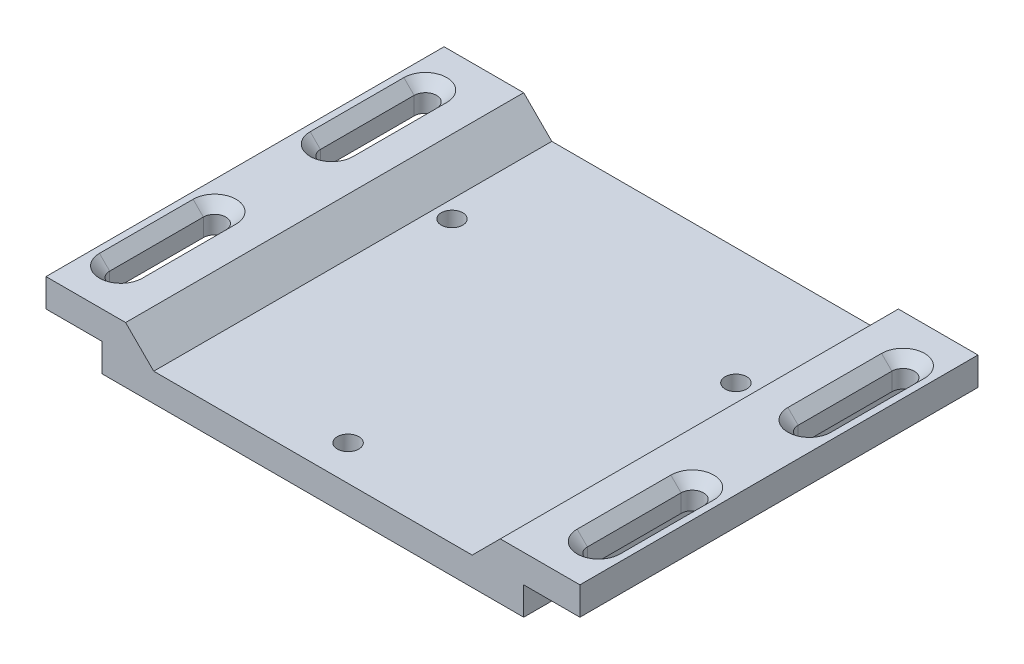
SolidWorks part; units mm, degrees
note: '?' marks a value the reader was unsure of. The reader was unsure of these and kept them because the rebuilt part matched: shared geometry of "Sketch16<4>".
ref_plane "Płaszczyzna przednia" through (0, 0, 0) normal (0, 0, 1) x (1, 0, 0)
ref_plane "Płaszczyzna górna" through (0, 0, 0) normal (0, 1, 0) x (1, 0, 0)
ref_plane "Płaszczyzna prawa" through (0, 0, 0) normal (1, 0, 0) x (0, 0, -1)
sketch "Sketch1" plane through (0, 0, 0) normal (0, 1, 0) x (1, 0, 0)
  line L1 (0, 0) -> (90, 0)
  line L2 (0, 0) -> (0, 85)
  line L3 (0, 85) -> (90, 85)
  line L4 (90, 0) -> (90, 85)
  dimension "D1" = 90
  dimension "D2" = 85
extrude "Boss-Extrude1" add sketch "Sketch1" along normal blind 6
fillet "Fillet1" [suppressed] radius 5
hole_wizard "Ø4.6 (4.6) Diameter Hole1" positions "Sketch4" profile "Sketch5" hole size "Ø4.6" standard "DIN" end condition through all
sketch "Sketch4" plane through (0, 6, 0) normal (0, 1, 0) x (1, 0, 0)
  line L1 (0, 85) -> (90, 85) construction
  line L2 (0, 85) -> (0, 0) construction
  line L3 (0, 0) -> (90, 0) construction
  line L4 (90, 85) -> (90, 0) construction
  line L5 (90, 85) -> (0, 85) construction
  line L6 (0, 85) -> (0, 0) construction
  line L7 (0, 0) -> (90, 85) construction
  line L9 (90, 0) -> (0, 85) construction
  line L10 (45, 40) -> (45, 5) construction
  line L11 (75.3109, 60) -> (14.6891, 60) construction
  circle A0 centre (45, 42.5) radius 35 construction
  point P81 (45, 7.5)
  point P88 (14.6891, 60)
  point P89 (75.3109, 60)
  dimension "D1" = 70
  dimension "D2" = 3
sketch "Sketch5" plane through (75.3109, 6, -60) normal (1, 0, 0) x (0, 0, 1)
  line L0 (0, 0) -> (0, 6)
  line L1 (0, 6) -> (2.3, 6)
  line L2 (2.3, 6) -> (2.3, 0)
  line L5 (2.3, 0) -> (0, 0)
  line L11 (0, -6.35) -> (0, 107.95) construction
  dimension "Thru Hole Dia." = 4.6
  dimension "Thru Hole Depth" = 6
hole_wizard "Ø4.6 (4.6) Diameter Hole2" [suppressed] positions "Sketch6" profile "Sketch7" hole size "Ø4.6" standard "DIN"
sketch "Sketch6" plane through (0, 6, 0) normal (0, 1, 0) x (1, 0, 0)
  line L0 (118, 0) -> (118, 75) construction
  line L1 (0, 0) -> (118, 0) construction
  line L2 (113, 80) -> (5, 80) construction
  point P0 (108, 8)
  point P6 (8, 8)
  point P7 (8, 28.6667)
  point P8 (8, 49.3333)
  point P9 (8, 70)
  point P10 (108, 28.6667)
  point P11 (108, 49.3333)
  point P12 (108, 70)
  dimension "D3" = 100
  dimension "D4" = 10
  dimension "D5" = 8
  dimension "D6" = 10
  dimension "D1" = 2
  dimension "D2" = 4
sketch "Sketch7" plane through (108, 6, -8) normal (1, 0, 0) x (0, 0, 1)
  line L0 (0, 0) -> (0, 6)
  line L1 (0, 6) -> (2.3, 6)
  line L2 (2.3, 6) -> (2.3, 0)
  line L5 (2.3, 0) -> (0, 0)
  line L11 (0, -6.35) -> (0, 107.95) construction
  dimension "Thru Hole Dia." = 4.6
  dimension "Thru Hole Depth" = 6
sketch "Sketch8" plane through (0, 0, 0) normal (0, 0, 1) x (1, 0, 0)
  line L7 (5, 12) -> (11, 6)
  line L8 (0, 6) -> (-12, 6)
  line L16 (5, 12) -> (-12, 12)
  line L17 (-12, 6) -> (-12, 12)
  line L18 (0, 6) -> (90, 6) construction
  line L19 (11, 6) -> (0, 6)
  line L20 (45, 6) -> (45, 27.9474) construction
  line L21 (79, 6) -> (90, 6)
  line L22 (85, 12) -> (79, 6)
  line L23 (85, 12) -> (102, 12)
  line L24 (102, 6) -> (102, 12)
  line L25 (90, 6) -> (102, 6)
  dimension "D2" = 12
  dimension "D3" = 45
  dimension "D4" = 17
  dimension "D1" = 6
extrude "Boss-Extrude2" add sketch "Sketch8" against normal up to surface (85 mm away) up to face at (45, 3, -85)
hole_wizard "CSK for M4 Hex Socket Countersunk Head Screw1" positions "Sketch14" profile "Sketch15" countersink size "M4" standard "DIN" end condition through all
sketch "Sketch14" plane through (0, 12, 0) normal (0, 1, 0) x (1, 0, 0)
  line L1 (-6, 75) -> (96, 75) construction
  line L2 (-6, 75) -> (-6, 10) construction
  line L3 (-6, 10) -> (96, 10) construction
  line L4 (96, 75) -> (96, 10) construction
  line L5 (90, 0) -> (90, 85) construction
  line L6 (90, 85) -> (102, 85) construction
  line L7 (102, 85) -> (102, 0) construction
  line L8 (102, 0) -> (90, 0) construction
  line L9 (-12, 85) -> (0, 85) construction
  line L10 (0, 85) -> (0, 0) construction
  line L11 (0, 0) -> (-12, 0) construction
  line L12 (-12, 0) -> (-12, 85) construction
  line L13 (90, 0) -> (90, 85)
  line L14 (90, 85) -> (102, 85)
  line L15 (102, 85) -> (102, 0)
  line L16 (102, 0) -> (90, 0)
  line L17 (-12, 85) -> (0, 85)
  line L18 (0, 85) -> (0, 0)
  line L19 (0, 0) -> (-12, 0)
  line L20 (-12, 0) -> (-12, 85)
  line L21 (-12, 10) -> (-6, 10) construction
  line L22 (-6, 10) -> (0, 10) construction
  line L24 (90, 10) -> (96, 10) construction
  line L25 (96, 10) -> (102, 10) construction
  line L26 (-12, 85) -> (-12, 0) construction
  line L27 (102, 85) -> (102, 0) construction
  line L28 (-6, 30) -> (96, 30)
  line L30 (96, 55) -> (-6, 55)
  point P0 (-6, 10)
  point P2 (-6, 75)
  point P4 (96, 75)
  point P6 (96, 10)
  point P106 (-6, 30)
  point P108 (-6, 55)
  point P110 (96, 55)
  point P112 (96, 30)
  dimension "D1" = 10
  dimension "D2" = 10
  dimension "D3" = 20
  dimension "D4" = 20
sketch "Sketch15" plane through (-6, 12, -10) normal (1, 0, 0) x (0, 0, 1)
  line L0 (0, 0) -> (0, 12)
  line L1 (0, 12) -> (2.4, 12)
  line L2 (2.4, 12) -> (2.4, 2.19)
  line L3 (2.4, 2.19) -> (4.59, 0)
  line L5 (4.59, 0) -> (0, 0)
  line L6 (-2.4, 2.19) -> (-4.59, 0) construction
  line L11 (0, -6.35) -> (0, 107.95) construction
  dimension "Thru Hole Dia." = 4.8
  dimension "Thru Hole Depth" = 12
  dimension "Near C'Sink Dia." = 9.18
  dimension "Near C'Sink Angle" = 90
ref_axis "Axis2" through (-6, 6, -10) along (0, 1, 0)?
ref_plane "Plane2" through (0, 0, -10) normal (0, 0, 1) x (0, 1, 0)
ref_axis "Axis3" through (-6, 6, -30) along (0, 1, 0)?
ref_plane "Plane3" through (0, 0, -30) normal (0, 0, 1) x (0, 1, 0)
ref_axis "Axis4" through (-6, 6, -55) along (0, 1, 0)?
ref_plane "Plane4" through (0, 0, -55) normal (0, 0, 1) x (0, 1, 0)
ref_axis "Axis5" through (-6, 6, -75) along (0, 1, 0)?
ref_plane "Plane5" through (0, 0, -75) normal (0, 0, -1) x (-1, 0, 0)
sketch "Sketch16" plane through (0, 0, -10) normal (0, 0, 1) x (0, 1, 0)
  line L0 (6, 8.4) -> (6, 3.6) construction
  line L2 (12, 1.41) -> (26, 24.59)
  line L3 (9.81, 3.6) -> (9.81, 8.4) construction
  line L4 (6, 8.4) -> (6, 3.6)
  line L5 (9.81, 3.6) -> (9.81, 8.4) construction
  line L6 (26, 24.59) -> (9.81, 8.4)
  line L7 (6, 8.4) -> (9.81, 8.4)
  line L8 (12, 1.41) -> (9.81, 3.6)
  line L9 (6, 3.6) -> (9.81, 3.6)
  line L10 (6, 8.4) -> (6, 3.6)
  line L12 (6, -45) -> (36.2962, -45) construction
  line L13 (6, -11) -> (6, -79) construction
  line L14 (12, -91.41) -> (9.81, -93.6)
  line L15 (26, -114.59) -> (9.81, -98.4)
  line L16 (6, -98.4) -> (9.81, -98.4)
  line L17 (6, -98.4) -> (6, -93.6)
  line L18 (6, -93.6) -> (9.81, -93.6)
  line L19 (12, -91.41) -> (26, -114.59)
  point P10 (10.905, 2.505)
  point P17 (10.905, -92.505)
extrude "Cut-Extrude1" cut sketch "Sketch16" against normal up to surface (20 mm away) from surface at 0 contours L4 L9 L8 L2 L6 L7 | L19 L14 L18 L17 L16 L15 up to plane "Plane3" starting at plane "Plane2"
extrude "Cut-Extrude2" cut sketch "Sketch16<4>" along normal up to surface (20 mm away) from surface at -65 contours L4 L9 L8 L2 L6 L7 | L15 L16 L17 L18 L14 L19 up to plane "Plane4" starting at plane "Plane5"
sketch "Sketch16<4>" plane through (0, 0, -10) normal (0, 0, 1) x (0, 1, 0) same geometry as "Sketch16"
equation "\"D6@Sketch6\"=\"D4@Sketch6\""
equation "\"D4@Sketch8\"=\"D2@Sketch8\"+5"
equation "\"D1@Sketch14\"=\"D2@Sketch14\""
